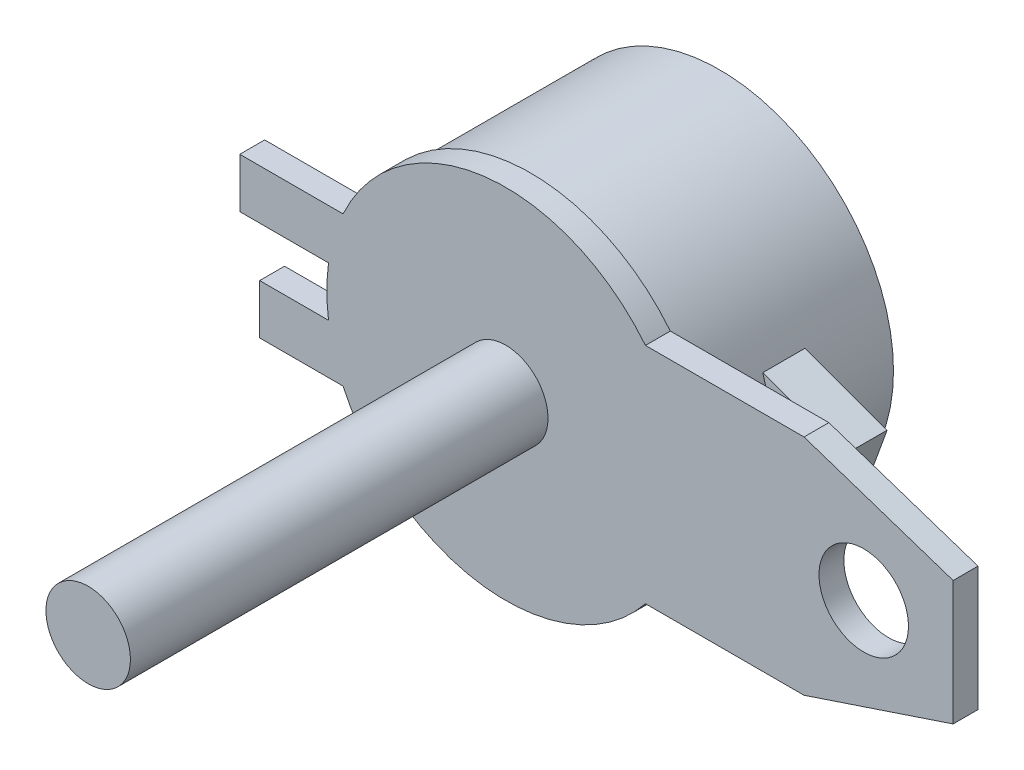
SolidWorks part; units mm, degrees
material "ABS"
ref_plane "Спереди" through (0, 0, 0) normal (0, 0, 1) x (1, 0, 0)
ref_plane "Сверху" through (0, 0, 0) normal (0, 1, 0) x (1, 0, 0)
ref_plane "Справа" through (0, 0, 0) normal (1, 0, 0) x (0, 0, -1)
ref_axis "Ось1" through (0, 0, -80.9) along (0, 0, 1)
sketch "Эскиз2" plane through (0, 0, 0) normal (0, 0, 1) x (1, 0, 0)
  circle A0 centre (0, 0) radius 3.5
  dimension "D1" = 7
extrude "Бобышка-Вытянуть2" add sketch "Эскиз2" along normal blind 4.3 separate body
sketch "Эскиз5" plane through (0, 0, 4.3) normal (0, 0, 1) x (1, 0, 0)
  line L0 (-4.95, -1.5) -> (-4.95, -0.5)
  line L1 (-4.95, -1.5) -> (-3.2726, -1.5)
  line L2 (-5.35, 1.5) -> (-3.2726, 1.5)
  line L3 (-4.95, -0.5) -> (-3.5651, -0.5)
  line L4 (-5.35, 1.5) -> (-5.35, 0.5)
  line L5 (-5.35, 0.5) -> (-3.5651, 0.5)
  line L6 (9, -1.25) -> (9, 1.25)
  line L7 (9, -1.25) -> (6, -2.25)
  line L8 (6, -2.25) -> (2.8102, -2.25)
  line L9 (9, 1.25) -> (6, 2.25)
  line L10 (6, 2.25) -> (2.8102, 2.25)
  circle A0 centre (0, 0) radius 3.6 construction
  arc A1 (-3.5651, -0.5) -> (-3.5651, 0.5) centre (0, 0) cw
  circle A2 centre (7.2012, 0.0033) radius 0.9
  arc A3 (-3.2726, 1.5) -> (2.8102, 2.25) centre (0, 0) cw
  arc A4 (2.8102, -2.25) -> (-3.2726, -1.5) centre (0, 0) cw
  point P11 (0, 0)
  point P20 (7.2012, 0.0033)
  point P21 (0, 0)
  point P22 (0.1103, 0)
  point P23 (0, 0)
  point P24 (-3.2726, -1.5)
  point P25 (-3.2726, 1.5)
  point P26 (-3.5651, 0.5)
  point P27 (-3.5651, -0.5)
  dimension "D1" = 7.2
  dimension "D7" = 9
  dimension "D12" = 1.8
  dimension "D14" = 4.95
  dimension "D2" = 5.35
  dimension "D3" = 3
  dimension "D4" = 1.5
  dimension "D5" = 1
  dimension "D6" = 1
  dimension "D8" = 1.25
  dimension "D9" = 2.5
  dimension "D10" = 2.25
  dimension "D11" = 6
  dimension "D13" = 7.2012
extrude "Бобышка-Вытянуть3" add sketch "Эскиз5" against normal blind 0.5
sketch "Эскиз6" plane through (0, 0, 4.3) normal (0, 0, 1) x (1, 0, 0)
  circle A0 centre (0, 0) radius 0.85
  dimension "D1" = 1.7
extrude "Бобышка-Вытянуть4" add sketch "Эскиз6" along normal blind 8.4
sketch "Эскиз7" plane through (0, 0, 4.3) normal (0, 0, 1) x (1, 0, 0)
  line L0 (3.4847, -3.5829) -> (4.9725, 0.5047)
  line L1 (3.4847, -3.5829) -> (1.8329, -2.9817)
  line L2 (4.9725, 0.5047) -> (3.3207, 1.106)
  line L3 (0, 0) -> (3.5, 0) construction
  line L4 (3.2889, -1.1971) -> (4.2286, -1.5391) construction
  circle A0 centre (0, 0) radius 3.5 construction
  arc A1 (2.681, -2.25) -> (3.1623, -1.5) centre (0, 0) ccw construction
  arc A2 (3.3207, 1.106) -> (1.8329, -2.9817) centre (0, 0) cw
  dimension "D1" = 4.5
  dimension "D2" = 4.35
  dimension "D3" = 20
extrude "Бобышка-Вытянуть5" add sketch "Эскиз7" against normal blind 0.85 from offset 1.85 offset against normal yes
